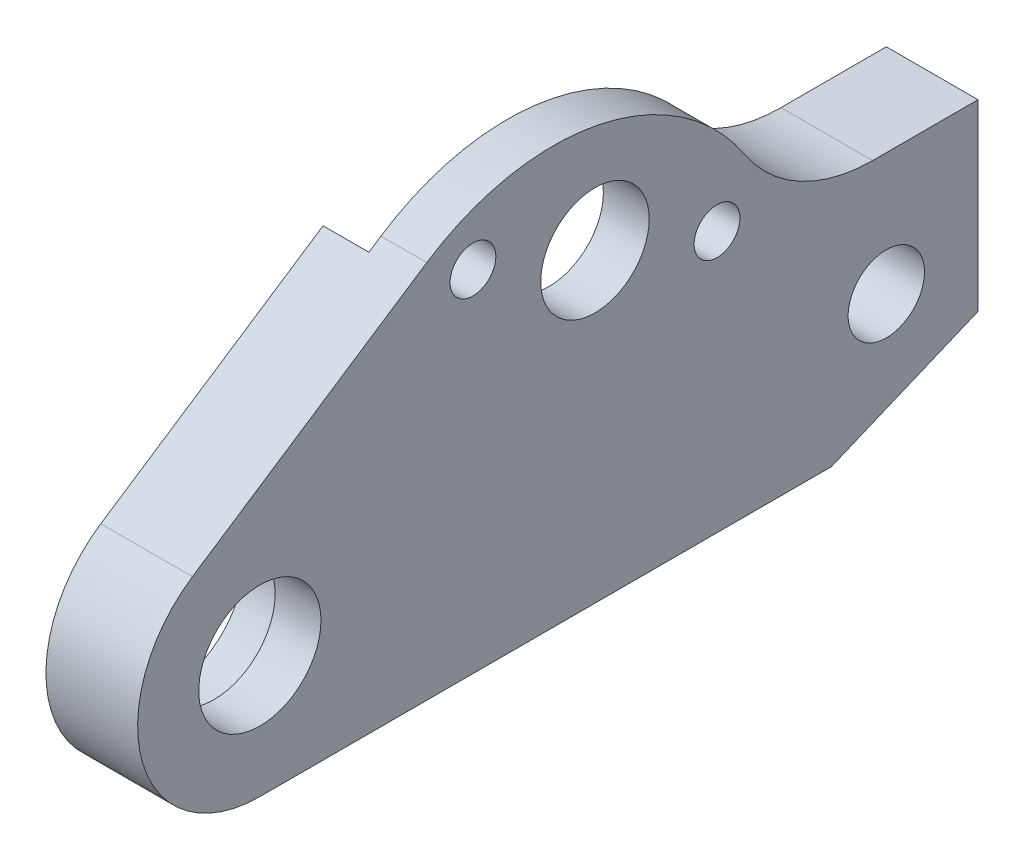
SolidWorks part; units mm, degrees
ref_plane "Front Plane" through (0, 0, 0) normal (0, 0, 1) x (1, 0, 0)
ref_plane "Top Plane" through (0, 0, 0) normal (0, 1, 0) x (1, 0, 0)
ref_plane "Right Plane" through (0, 0, 0) normal (1, 0, 0) x (0, 0, -1)
sketch "Sketch1" plane through (0, 0, 0) normal (1, 0, 0) x (0, 0, -1)
  line L0 (-4.4103, 6.6745) -> (10.925, 16.8075)
  line L1 (37.4, -8) -> (47, -4)
  line L2 (47, -4) -> (47, 8)
  line L3 (29.9191, 9.0928) -> (13.9443, 14.9072) construction
  line L4 (47, 8) -> (40.1015, 8)
  line L5 (37.4, -8) -> (0, -8)
  line L6 (-9, -42) -> (51, -42) construction
  line L7 (-9, -42) -> (-9, 16) construction
  line L8 (-9, 16) -> (51, 16) construction
  line L9 (51, -42) -> (51, 16) construction
  arc A0 (-4.4103, 6.6745) -> (0, -8) centre (0, 0) ccw
  circle A1 centre (21.9317, 12) radius 12.5 construction
  arc A2 (31.7386, 12.5171) -> (10.925, 16.8075) centre (19.1943, 4.2928) ccw
  circle A3 centre (21.9317, 12) radius 3.55
  circle A4 centre (41, 0) radius 6 construction
  circle A5 centre (0, 0) radius 4
  circle A6 centre (41, 0) radius 2.5
  circle A7 centre (29.9191, 9.0928) radius 1.5
  circle A8 centre (13.9443, 14.9072) radius 1.5
  circle A9 centre (29.9191, 9.0928) radius 3.25 construction
  circle A10 centre (13.9443, 14.9072) radius 3.25 construction
  arc A11 (40.1015, 8) -> (31.7386, 12.5171) centre (40.1015, 18) cw
  dimension "D5" = 5
  dimension "D6" = 8
  dimension "D7" = 8
  dimension "D8" = 25
  dimension "D10" = 7.1
  dimension "D14" = 15
  dimension "D15" = 3
  dimension "D17" = 6.5
  dimension "D18" = 10
  dimension "D20" = 12
  dimension "D1" = 60
  dimension "D2" = 58
  dimension "D3" = 42
  dimension "D4" = 9
  dimension "D9" = 12
  dimension "D11" = 25
  dimension "D12" = 42
  dimension "D13" = 50
  dimension "D16" = 8.5
  dimension "D19" = 20
  dimension "D21" = 12
  dimension "D23" = 8
extrude "Boss-Extrude1" add sketch "Sketch1" along normal blind 6
sketch "Sketch2" plane through (0, 0, 0) normal (1, 0, 0) x (0, 0, -1)
  circle A0 centre (0, 0) radius 4.99
  dimension "D1" = 9.98
extrude "Cut-Extrude1" cut sketch "Sketch2" along normal blind 3
sketch "Sketch3" plane through (0, 0, 0) normal (1, 0, 0) x (0, 0, -1)
  circle A0 centre (21.9317, 12) radius 12.55
  dimension "D1" = 25.1
extrude "Cut-Extrude2" cut sketch "Sketch3" along normal blind 3
